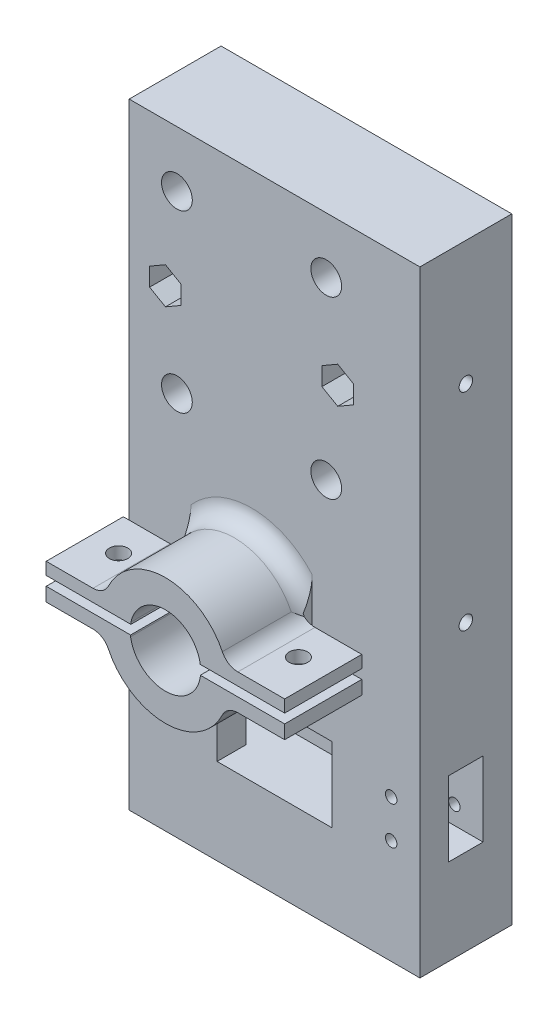
SolidWorks part; units mm, degrees
other "Markup1"
sketch "Sketch8" plane through (21.3115, 25, 0) normal (0.306, 0.1864, -0.9336) x (-0.9512, 0.0181, -0.3081)
ref_plane "Front Plane" through (0, 0, 0) normal (0, 0, 1) x (1, 0, 0)
ref_plane "Top Plane" through (0, 0, 0) normal (0, 1, 0) x (1, 0, 0)
ref_plane "Right Plane" through (0, 0, 0) normal (1, 0, 0) x (0, 0, -1)
sketch "Sketch1" plane through (0, 0, 0) normal (0, 0, 1) x (1, 0, 0)
  line L0 (0, 25) -> (0, -25) construction
  line L1 (21.3115, 25) -> (-21.3115, 25)
  line L2 (21.3115, 25) -> (21.3115, -25)
  line L3 (21.3115, -25) -> (-21.3115, -25)
  line L4 (-21.3115, 25) -> (-21.3115, -25)
  line L5 (21.3115, 25) -> (-21.3115, -25) construction
  line L6 (21.3115, -25) -> (-21.3115, 25) construction
  line L7 (-21.3115, 0) -> (21.3115, 0) construction
  circle A0 centre (-13, -15.25) radius 2.677
  circle A1 centre (13, -15.25) radius 2.677
  circle A2 centre (13, 15.25) radius 2.677
  circle A3 centre (-13, 15.25) radius 2.677
  point P0 (0, 0)
  dimension "D1" = 30.5
  dimension "D2" = 26
  dimension "D3" = 50
extrude "Boss-Extrude1" add sketch "Sketch1" along normal blind 16
sketch "Sketch2" plane through (0, 0, 0) normal (0, 0, 1) x (1, 0, 0)
  circle A0 centre (0, 0) radius 11.04
  dimension "D1" = 22.08
extrude "Cut-Extrude2" cut sketch "Sketch2" along normal blind 11
sketch "Sketch3" plane through (0, 0, 0) normal (0, 0, -1) x (-1, 0, 0)
  line L0 (0, 0) -> (-18.0234, 0) construction
  line L1 (0, 0) -> (0, 5.0894) construction
  circle A0 centre (-15, 0) radius 1.75
  circle A1 centre (15, 0) radius 1.75
  dimension "D1" = 15
  dimension "D2" = 3.5
extrude "Cut-Extrude3" cut sketch "Sketch3" against normal blind 10
sketch "Sketch9" plane through (0, 0, 0) normal (0, 0, -1) x (-1, 0, 0)
  line L0 (0, -11.04) -> (0, 11.04) construction
  line L1 (-15, 3.1754) -> (-17.75, 1.5877)
  line L2 (-17.75, 1.5877) -> (-17.75, -1.5877)
  line L3 (-17.75, -1.5877) -> (-15, -3.1754)
  line L4 (-15, -3.1754) -> (-12.25, -1.5877)
  line L5 (-12.25, -1.5877) -> (-12.25, 1.5877)
  line L6 (-12.25, 1.5877) -> (-15, 3.1754)
  line L7 (12.25, 1.5877) -> (15, 3.1754)
  line L8 (12.25, -1.5877) -> (12.25, 1.5877)
  line L9 (15, -3.1754) -> (12.25, -1.5877)
  line L10 (17.75, -1.5877) -> (15, -3.1754)
  line L11 (17.75, 1.5877) -> (17.75, -1.5877)
  line L12 (15, 3.1754) -> (17.75, 1.5877)
  circle A0 centre (-15, 0) radius 2.75 construction
  circle A1 centre (0, 0) radius 11.04 construction
  point P1 (-17.75, 0)
  dimension "D1" = 5.5
extrude "Cut-Extrude6" cut sketch "Sketch9" against normal through all from offset 5 offset against normal yes
sketch "Sketch30" plane through (0, -25, 0) normal (0, -1, 0) x (1, 0, 0)
  line L1 (-21.3115, 16) -> (21.3115, 16)
  line L2 (-21.3115, 16) -> (-21.3115, 0)
  line L3 (-21.3115, 0) -> (21.3115, 0)
  line L4 (21.3115, 16) -> (21.3115, 0)
extrude "Boss-Extrude8" add sketch "Sketch30" along normal blind 20.23
sketch "Sketch10" plane through (0, 0, 0) normal (0, 0, 1) x (1, 0, 0)
  line L0 (21.3115, -45.23) -> (-21.3115, -45.23)
  line L2 (-21.3115, -45.23) -> (-21.3115, -67.23)
  line L3 (-21.3115, -67.23) -> (21.3115, -67.23)
  line L4 (21.3115, -67.23) -> (21.3115, -45.23)
  dimension "D1" = 22
extrude "Boss-Extrude2" add sketch "Sketch10" along normal up to surface (16 mm away) up to face at (15, 0, 16)
sketch "Sketch14" plane through (-21.3115, 0, 0) normal (-1, 0, 0) x (0, 0, 1)
  line L0 (16, -67.23) -> (0, -67.23) construction
  line L1 (5, -67.23) -> (11, -67.23)
  line L2 (5, -67.23) -> (5, -54.23)
  line L3 (5, -54.23) -> (11, -54.23)
  line L4 (11, -67.23) -> (11, -54.23)
  line L7 (0, -67.23) -> (16, -67.23) construction
  point P6 (8, -67.23)
  point P7 (8, -67.23)
  dimension "D1" = 13
  dimension "D2" = 6
extrude "Cut-Extrude7" cut sketch "Sketch14" against normal through all
sketch "Sketch16" plane through (21.3115, 0, 0) normal (1, 0, 0) x (0, 0, -1)
  line L0 (-8, -54.23) -> (-8, 25)
  line L1 (-11, -54.23) -> (-5, -54.23) construction
  line L2 (-16, 25) -> (0, 25) construction
  line L4 (-16, 25) -> (0, 25)
  line L5 (-16, 25) -> (-16, -54.23)
  line L6 (-16, -54.23) -> (0, -54.23)
  line L7 (0, 25) -> (0, -54.23)
  line M6 (-11, -54.23) -> (-5, -54.23)
  line M9 (0, -67.23) -> (0, 25)
  line M10 (0, 25) -> (-16, 25)
  line M11 (-16, 25) -> (-16, -67.23)
extrude "Boss-Extrude3" add sketch "Sketch16" along normal blind 8 contours L6 L0 M11 M6 M10 | L6 L0 M6 M9 M10
sketch "Sketch17" plane through (29.3115, 0, 0) normal (1, 0, 0) x (0, 0, -1)
  line L0 (-8, -54.23) -> (-8, 25)
  line L1 (-16, -54.23) -> (0, -54.23) construction
  line L2 (0, 25) -> (-16, 25) construction
  line L3 (-8, -14.615) -> (0, -14.615)
  line L4 (0, -54.23) -> (0, 25) construction
  circle A0 centre (-8, 3.385) radius 1.175
  circle A1 centre (-8, -32.615) radius 1.175
  point P8 (-8, -14.615)
  dimension "D2" = 2.35
  dimension "D1" = 18
extrude "Cut-Extrude9" cut sketch "Sketch17" against normal blind 8 contours L0 A0 | L0 A0 | A1 L0 | A1 L0
sketch "Sketch18" plane through (0, 0, 0) normal (0, 0, -1) x (-1, 0, 0)
  line L0 (-25.3115, -54.23) -> (-25.3115, 25)
  line L1 (-29.3115, -54.23) -> (-21.3115, -54.23) construction
  line L2 (-29.3115, 25) -> (21.3115, 25) construction
  line L3 (-25.3115, -14.615) -> (-29.3115, -14.615)
  line L4 (-26.2115, 5.385) -> (-24.4115, 5.385)
  line L5 (-26.2115, 5.385) -> (-26.2115, 1.385)
  line L6 (-26.2115, 1.385) -> (-24.4115, 1.385)
  line L7 (-24.4115, 5.385) -> (-24.4115, 1.385)
  line L8 (-26.2115, 5.385) -> (-24.4115, 1.385) construction
  line L9 (-26.2115, 1.385) -> (-24.4115, 5.385) construction
  line L10 (-29.3115, -54.23) -> (-29.3115, 25) construction
  line L11 (-26.2115, -30.615) -> (-24.4115, -30.615)
  line L12 (-24.4115, -34.615) -> (-24.4115, -30.615)
  line L13 (-26.2115, -34.615) -> (-24.4115, -34.615)
  line L14 (-26.2115, -34.615) -> (-26.2115, -30.615)
  point P6 (-25.3115, 3.385)
  point P11 (-25.3115, -14.615)
  dimension "D1" = 18
  dimension "D2" = 4
  dimension "D3" = 1.8
extrude "Cut-Extrude10" cut sketch "Sketch18" against normal blind 10.2 contours L7 L4 L0 L6 | L5 L6 L0 L4 | L14 L11 L12 L13
sketch "Sketch15" plane through (0, 0, 0) normal (0, 0, -1) x (-1, 0, 0)
  line L0 (21.3115, -67.23) -> (-21.3115, -67.23) construction
  line L1 (-29.3115, -23.2996) -> (21.3115, -23.2996)
  line L2 (-21.3115, -67.23) -> (-21.3115, -54.23)
  line L3 (-29.3115, -54.23) -> (-29.3115, 25) construction
  line L4 (-4, -23.2996) -> (-4, -67.23)
  line L7 (-21.3115, -67.23) -> (-21.3115, -54.23) construction
  line L8 (-21.3115, -54.23) -> (-21.3115, -67.23) construction
  line L9 (-21.3115, -60.73) -> (21.3115, -60.73)
  line L10 (21.3115, 25) -> (21.3115, -67.23) construction
  line L11 (21.3115, -60.73) -> (21.3115, -28)
  line L12 (21.3115, -28) -> (0, -28)
  line L13 (0, -28) -> (0, -67.23)
  circle A2 centre (16.3115, -64.03) radius 1
  circle A4 centre (16.3115, -57.43) radius 1
  point P11 (-21.3115, -67.23)
  dimension "D1" = 5
  dimension "D2" = 3.2
extrude "Cut-Extrude8" cut sketch "Sketch15" against normal through all and the other way through all
sketch "Sketch6" plane through (0, -54.23, 0) normal (0, -1, 0) x (1, 0, 0)
  line L0 (21.3115, 11) -> (-21.3115, 11) construction
  line L1 (4.517, 11) -> (-4.517, 11)
  line L2 (4.517, 11) -> (4.517, 14.85)
  line L3 (4.517, 14.85) -> (-4.517, 14.85)
  line L4 (-4.517, 11) -> (-4.517, 14.85)
  line L5 (4.517, 11) -> (-4.517, 14.85) construction
  line L6 (4.517, 14.85) -> (-4.517, 11) construction
  point P0 (0, 12.925)
  dimension "D1" = 3.85
extrude "Cut-Extrude5" cut sketch "Sketch6" against normal blind 50 and the other way through all
sketch "Sketch20" plane through (0, -54.23, 0) normal (0, -1, 0) x (-1, 0, 0)
  line L1 (-21.3115, -16) -> (-29.3115, -16)
  line L2 (-21.3115, -16) -> (-21.3115, 0)
  line L3 (-21.3115, 0) -> (-29.3115, 0)
  line L4 (-29.3115, -16) -> (-29.3115, 0)
extrude "Boss-Extrude5" add sketch "Sketch20" along normal up to surface (13 mm away) up to face at (0, -67.23, 13.2125)
sketch "Sketch21" plane through (0, -67.23, 0) normal (0, -1, 0) x (-1, 0, 0)
  line L0 (-29.3115, -16) -> (-29.3115, 0) construction
  line L1 (-21.3115, -11) -> (-29.3115, -11)
  line L2 (-21.3115, -11) -> (-21.3115, -5)
  line L3 (-21.3115, -5) -> (-29.3115, -5)
  line L4 (-29.3115, -11) -> (-29.3115, -5)
extrude "Cut-Extrude11" cut sketch "Sketch21" against normal up to surface (13 mm away) up to face at (0, -54.23, 9)
sketch "Sketch22" plane through (0, 0, 0) normal (0, 0, -1) x (-1, 0, 0)
  line L0 (21.3115, -67.23) -> (-29.3115, -67.23) construction
  line L1 (-29.3115, -67.23) -> (-29.3115, 25) construction
  circle A0 centre (-24.3115, -64.03) radius 1
  circle A3 centre (-24.3115, -57.43) radius 1
  dimension "D1" = 2
  dimension "D2" = 3.2
  dimension "D3" = 5
  dimension "D4" = 6.6
  dimension "D5" = 2
  dimension "D6" = 5
extrude "Cut-Extrude12" cut sketch "Sketch22" against normal through all
sketch "Sketch24" plane through (0, -67.23, 0) normal (0, -1, 0) x (1, 0, 0)
  line L1 (-21.3115, 5) -> (29.3115, 5)
  line L2 (-21.3115, 5) -> (-21.3115, 0)
  line L3 (-21.3115, 0) -> (29.3115, 0)
  line L4 (29.3115, 5) -> (29.3115, 0)
extrude "Boss-Extrude6" add sketch "Sketch24" along normal blind 15
sketch "Sketch25" plane through (0, 0, 5) normal (0, 0, 1) x (1, 0, 0)
  line L0 (29.3115, -82.23) -> (-21.3115, -82.23) construction
  line L1 (-21.3115, -82.23) -> (29.3115, -82.23)
  line L2 (-21.3115, -82.23) -> (-21.3115, -67.23)
  line L3 (-21.3115, -67.23) -> (29.3115, -67.23)
  line L4 (29.3115, -82.23) -> (29.3115, -67.23)
extrude "Boss-Extrude7" add sketch "Sketch25" along normal up to surface (11 mm away) up to face at (23.3115, -64.03, 16)
sketch "Sketch26" plane through (0, -82.23, 0) normal (0, -1, 0) x (1, 0, 0)
  line L0 (4, 16) -> (4, 0)
  line L1 (29.3115, 16) -> (-21.3115, 16) construction
  line L2 (-21.3115, 0) -> (29.3115, 0) construction
  line L3 (4, 8) -> (-21.3115, 8)
  line L4 (-21.3115, 16) -> (-21.3115, 0) construction
  circle A0 centre (-14, 8) radius 1
  circle A1 centre (22, 8) radius 1
  dimension "D1" = 2
  dimension "D2" = 18
extrude "Cut-Extrude13" cut sketch "Sketch26" against normal blind 10 contours L3 A0 | L3 A0 | A1
sketch "Sketch27" plane through (0, 0, 0) normal (0, 0, -1) x (-1, 0, 0)
  line L0 (-24.4115, -34.615) -> (-24.4115, -30.615) construction
  line L1 (-24.0015, -77.33) -> (-20.0015, -77.33)
  line L2 (-24.0015, -77.33) -> (-24.0015, -79.13)
  line L3 (-24.0015, -79.13) -> (-20.0015, -79.13)
  line L4 (-20.0015, -77.33) -> (-20.0015, -79.13)
  line L5 (-24.0015, -77.33) -> (-20.0015, -79.13) construction
  line L6 (-24.0015, -79.13) -> (-20.0015, -77.33) construction
  line L8 (-26.2115, -34.615) -> (-24.4115, -34.615) construction
  line L12 (-29.3115, -82.23) -> (-29.3115, 25) construction
  line L13 (21.3115, -82.23) -> (-29.3115, -82.23) construction
  line L14 (-29.3115, -49.5626) -> (21.3115, -49.5626)
  line L15 (21.3115, 25) -> (21.3115, -82.23) construction
  line L16 (-4, -49.5626) -> (-4, -82.23)
  line L17 (16.0015, -79.13) -> (12.0015, -79.13)
  line L18 (12.0015, -77.33) -> (12.0015, -79.13)
  line L19 (16.0015, -77.33) -> (12.0015, -77.33)
  line L20 (16.0015, -77.33) -> (16.0015, -79.13)
  point P0 (-22.0015, -78.23)
  dimension "D1" = 7.31
  dimension "D2" = 3.1
extrude "Cut-Extrude14" cut sketch "Sketch27" against normal blind 10.2 contours L4 L1 L2 L3 | L20 L19 L18 L17
sketch "Sketch29" plane through (0, 0, 16) normal (0, 0, 1) x (1, 0, 0)
  line L0 (-16.3115, -57.43) -> (24.3115, -64.03)
  line L1 (24.3115, -57.43) -> (-16.3115, -64.03)
  line L2 (-16.3115, -57.43) -> (24.3115, -57.43)
  line L3 (-16.3115, -57.43) -> (-16.3115, -64.03)
  line L4 (-16.3115, -64.03) -> (24.3115, -64.03)
  line L5 (24.3115, -57.43) -> (24.3115, -64.03)
  line L7 (-6, -54.23) -> (14, -54.23)
  line L8 (-6, -54.23) -> (-6, -67.23)
  line L9 (-6, -67.23) -> (14, -67.23)
  line L10 (14, -54.23) -> (14, -67.23)
  line L11 (-6, -54.23) -> (14, -67.23) construction
  line L12 (-6, -67.23) -> (14, -54.23) construction
  circle A0 centre (-16.3115, -57.43) radius 1 construction
  point P4 (4, -60.73)
  dimension "D1" = 13
  dimension "D2" = 20
extrude "Cut-Extrude15" cut sketch "Sketch29" against normal up to surface (5 mm away) contours L10 L7 L8 L2 | L10 L2 L8 L0 L1 | L0 L8 L1 | L10 L4 L8 L9 | L10 L0 L1 L8 L4 | L10 L1 L0 up to face at (-16.3115, -65.03, 11)
sketch "Sketch31" plane through (0, 0, 0) normal (0, 0, -1) x (-1, 0, 0)
  line L5 (-4.5, 14.04) -> (4.5, 14.04)
  line L6 (-4.5, 14.04) -> (-4.5, 8.04)
  line L7 (-4.5, -8.04) -> (4.5, -8.04)
  line L8 (-4.5, -8.04) -> (-4.5, -14.04)
  line L9 (-4.5, -14.04) -> (4.5, -14.04)
  line L10 (4.5, -8.04) -> (4.5, -14.04)
  line L11 (-4.5, -8.04) -> (4.5, -14.04) construction
  line L12 (-4.5, -14.04) -> (4.5, -8.04) construction
  line L13 (-4.5, 8.04) -> (4.5, 8.04)
  line L14 (4.5, 14.04) -> (4.5, 8.04)
  line L15 (-4.5, 14.04) -> (4.5, 8.04) construction
  line L16 (-4.5, 8.04) -> (4.5, 14.04) construction
  circle A1 centre (0, 0) radius 11.04 construction
  point P0 (-11.04, 0)
  point P1 (0, 11.04)
  point P8 (0, -11.04)
  dimension "D1" = 6
  dimension "D2" = 9
  dimension "D3" = 9
  dimension "D4" = 6
extrude "Cut-Extrude16" cut sketch "Sketch31" against normal up to surface (11 mm away) up to face at (0, -1.8734, 11)
sketch "Sketch32" plane through (0, 0, 16) normal (0, 0, 1) x (1, 0, 0)
  line L24 (10.5609, -36.9231) -> (20.76, -36.9231)
  line L25 (-19.1881, -39.0641) -> (-6.0144, -39.0641)
  line L27 (-18.3513, -40.6918) -> (-6.0688, -40.6918)
  line L29 (-6.0144, -38.7401) -> (-6.0144, -39.0641)
  line L30 (-6.0688, -40.9648) -> (-6.0688, -40.6918)
  line L31 (6.0688, -40.9648) -> (6.0688, -40.6918)
  line L32 (6.0239, -39.0641) -> (6.0144, -38.7401)
  line L33 (6.0239, -39.0641) -> (17.5144, -39.0641)
  line L34 (6.0688, -40.6918) -> (18.3513, -40.6918)
  line L35 (-20.76, -36.9231) -> (-10.5609, -36.9231)
  line L36 (-20.76, -36.9231) -> (-20.76, -39.0641)
  line L37 (-20.76, -43.0769) -> (-10.5609, -43.0769)
  line L38 (20.76, -36.9231) -> (20.76, -39.0641)
  line L39 (10.5609, -43.0769) -> (20.76, -43.0769)
  line L40 (-19.1881, -39.0641) -> (-20.76, -39.0641)
  line L41 (-18.3513, -40.6918) -> (-20.76, -40.6918)
  line L42 (17.5144, -39.0641) -> (20.76, -39.0641)
  line L43 (18.3513, -40.6918) -> (20.76, -40.6918)
  line L44 (-20.76, -40.6918) -> (-20.76, -43.0769)
  line L45 (20.76, -40.6918) -> (20.76, -43.0769)
  line L46 (0, 0) -> (0, -82.23) construction
  line L47 (29.3115, -82.23) -> (-21.3115, -82.23) construction
  arc A0 (-6.0688, -40.9648) -> (6.0688, -40.9648) centre (0, -40) ccw
  arc A1 (-10.5609, -43.0769) -> (10.5609, -43.0769) centre (0, -40) ccw
  arc A2 (10.5609, -36.9231) -> (-10.5609, -36.9231) centre (0, -40) ccw
  arc A3 (6.0144, -38.7401) -> (-6.0144, -38.7401) centre (0, -40) ccw
  dimension "D2" = 6.145
  dimension "D1" = 40
extrude "Boss-Extrude9" add sketch "Sketch32" along normal blind 15
sketch "Sketch35" plane through (0, 0, 16) normal (0, 0, 1) x (1, 0, 0)
  line L0 (0, 0) -> (0, -82.23) construction
  line L1 (29.3115, -82.23) -> (-21.3115, -82.23) construction
  circle A0 centre (0, -40) radius 6.145
  dimension "D1" = 12.29
  dimension "D2" = 40
extrude "Cut-Extrude17" cut sketch "Sketch35" against normal through all
sketch "Sketch46" plane through (0, -82.23, 0) normal (0, -1, 0) x (1, 0, 0)
  line L0 (29.3115, 16) -> (-21.3115, 16) construction
  line L2 (-20.76, 31) -> (-20.76, 16) construction
  line L3 (20.76, 31) -> (20.76, 16) construction
  circle A0 centre (-15.66, 23.5) radius 1.6
  circle A1 centre (15.66, 23.5) radius 1.6
  dimension "D1" = 7.5
  dimension "D3" = 5.1
  dimension "D2" = 5.1
extrude "Cut-Extrude29" cut sketch "Sketch46" against normal through all
sketch "Sketch47" plane through (0, 0, 0) normal (0, 1, 0) x (1, 0, 0)
  line L0 (-10.5609, -31) -> (-10.5609, -16) construction
  line L1 (-20.76, -16) -> (-10.5609, -16)
  line L2 (-20.76, -16) -> (-20.76, -17.5701)
  line L3 (-20.76, -17.5701) -> (-10.5609, -17.5701)
  line L4 (-10.5609, -16) -> (-10.5609, -17.5701)
  line L5 (0, 0) -> (0, -33.2951) construction
  line L6 (20.76, -17.5701) -> (10.5609, -17.5701)
  line L7 (10.5609, -16) -> (10.5609, -17.5701)
  line L8 (20.76, -16) -> (10.5609, -16)
  line L9 (20.76, -16) -> (20.76, -17.5701)
extrude "Cut-Extrude30" cut sketch "Sketch47" against normal through all
fillet "Fillet1" radius 3 2 edges at (0, -29, 16) (0, -51, 16)
fillet "Fillet2" radius 3 4 edges at (-10.5609, -43.0769, 25) (-10.5609, -36.9231, 25) (10.5609, -36.9231, 25) (10.5609, -43.0769, 25)
